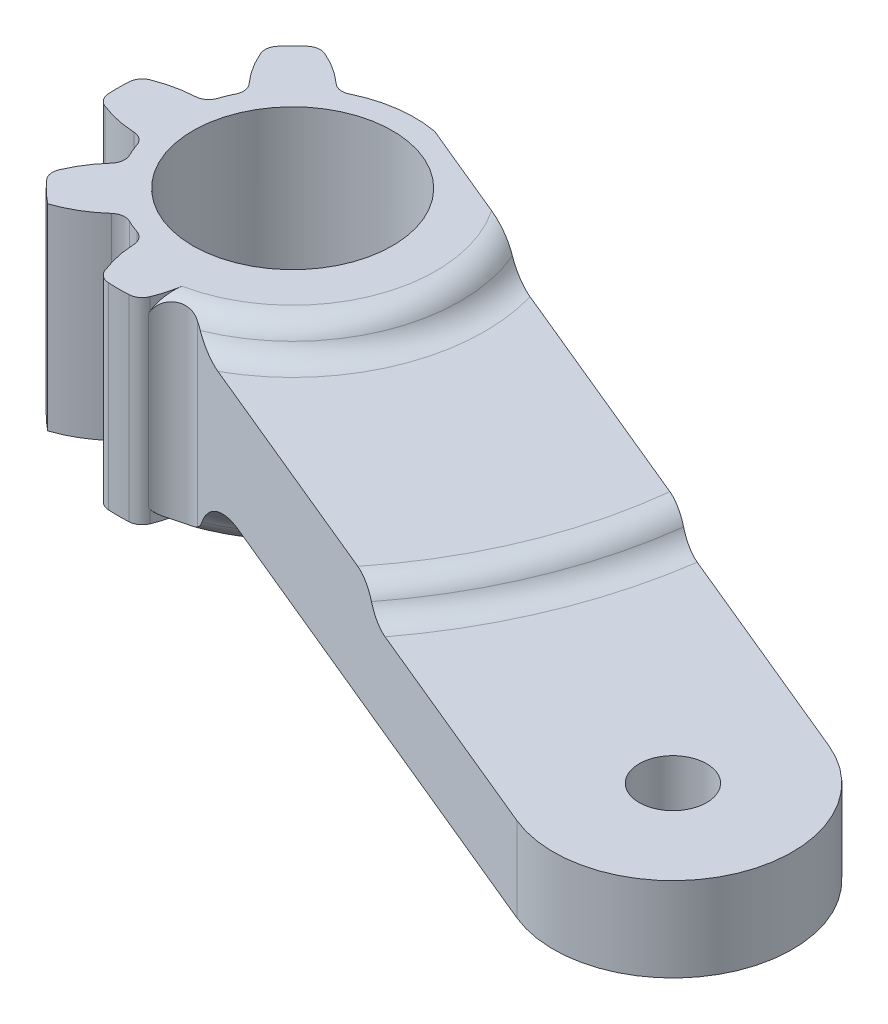
SolidWorks part; units mm, degrees
ref_plane "Front Plane" through (0, 0, 0) normal (0, 0, 1) x (1, 0, 0)
ref_plane "Top Plane" through (0, 0, 0) normal (0, 1, 0) x (1, 0, 0)
ref_plane "Right Plane" through (0, 0, 0) normal (1, 0, 0) x (0, 0, -1)
sketch "Sketch1" plane through (0, 0, 0) normal (0, 1, 0) x (1, 0, 0)
  line L0 (0, -4.35) -> (0, 4.35) construction
  line L3 (-3, 4.35) -> (3, 4.35) construction
  circle A2 centre (0, 0) radius 5.35 construction
  circle A3 centre (0, 10.7) radius 5.35 construction
  circle A4 centre (0, 10.7) radius 6.1 construction
  circle A5 centre (0, 10.7) radius 4.35 construction
  arc A7 (-3.9161, 1.8939) -> (-4.1083, 1.4299) centre (0, 0) ccw
  arc A8 (-0.8055, 5.8758) -> (-1.0948, 4.5554) centre (3, 4.35) ccw
  arc A9 (1.0948, 4.5554) -> (0.8055, 5.8758) centre (-3, 4.35) ccw
  arc A10 (0.3714, 6.1889) -> (-0.3714, 6.1889) centre (0, 0) ccw
  arc A11 (3.9954, 2.447) -> (4.7244, 3.5853) centre (0.9546, 5.1972) ccw
  arc A12 (4.6388, 4.1136) -> (4.1136, 4.6388) centre (0, 0) ccw
  arc A13 (3.5853, 4.7244) -> (2.447, 3.9954) centre (5.1972, 0.9546) ccw
  arc A14 (4.5554, -1.0948) -> (5.8758, -0.8055) centre (4.35, 3) ccw
  arc A15 (6.1889, -0.3714) -> (6.1889, 0.3714) centre (0, 0) ccw
  arc A16 (5.8758, 0.8055) -> (4.5554, 1.0948) centre (4.35, -3) ccw
  arc A17 (2.447, -3.9954) -> (3.5853, -4.7244) centre (5.1972, -0.9546) ccw
  arc A18 (4.1136, -4.6388) -> (4.6388, -4.1136) centre (0, 0) ccw
  arc A19 (4.7244, -3.5853) -> (3.9954, -2.447) centre (0.9546, -5.1972) ccw
  arc A20 (-1.0948, -4.5554) -> (-0.8055, -5.8758) centre (3, -4.35) ccw
  arc A21 (-0.3714, -6.1889) -> (0.3714, -6.1889) centre (0, 0) ccw
  arc A22 (0.8055, -5.8758) -> (1.0948, -4.5554) centre (-3, -4.35) ccw
  arc A23 (-3.9954, -2.447) -> (-4.7244, -3.5853) centre (-0.9546, -5.1972) ccw
  arc A24 (-4.6388, -4.1136) -> (-3.8788, -4.8368) centre (0, 0) ccw
  arc A25 (-3.8788, -4.8368) -> (-2.447, -3.9954) centre (-5.1972, -0.9546) ccw
  arc A26 (-4.5554, 1.0948) -> (-5.8758, 0.8055) centre (-4.35, -3) ccw
  arc A27 (-6.1889, 0.3714) -> (-6.1889, -0.3714) centre (0, 0) ccw
  arc A28 (-5.8758, -0.8055) -> (-4.5554, -1.0948) centre (-4.35, 3) ccw
  arc A29 (-2.447, 3.9954) -> (-3.5853, 4.7244) centre (-5.1972, 0.9546) ccw
  arc A30 (-4.1136, 4.6388) -> (-4.6388, 4.1136) centre (0, 0) ccw
  arc A31 (-4.7244, 3.5853) -> (-3.9954, 2.447) centre (-0.9546, 5.1972) ccw
  arc A32 (-4.1083, -1.4299) -> (-3.9161, -1.8939) centre (0, 0) ccw
  arc A33 (-1.8939, -3.9161) -> (-1.4299, -4.1083) centre (0, 0) ccw
  arc A34 (1.4299, -4.1083) -> (1.8939, -3.9161) centre (0, 0) ccw
  arc A35 (3.9161, -1.8939) -> (4.1083, -1.4299) centre (0, 0) ccw
  arc A36 (4.1083, 1.4299) -> (3.9161, 1.8939) centre (0, 0) ccw
  arc A37 (1.8939, 3.9161) -> (1.4299, 4.1083) centre (0, 0) ccw
  arc A38 (-1.4299, 4.1083) -> (-1.8939, 3.9161) centre (0, 0) ccw
  arc A39 (3.9954, -2.447) -> (3.9161, -1.8939) centre (4.3662, -2.1116) cw
  arc A40 (2.447, -3.9954) -> (1.8939, -3.9161) centre (2.1116, -4.3662) ccw
  arc A41 (-0.8055, -5.8758) -> (-0.3714, -6.1889) centre (-0.3414, -5.6898) ccw
  arc A42 (0.3714, -6.1889) -> (0.8055, -5.8758) centre (0.3414, -5.6898) ccw
  arc A43 (3.5853, -4.7244) -> (4.1136, -4.6388) centre (3.7819, -4.2647) ccw
  arc A44 (4.6388, -4.1136) -> (4.7244, -3.5853) centre (4.2647, -3.7819) ccw
  arc A45 (5.8758, -0.8055) -> (6.1889, -0.3714) centre (5.6898, -0.3414) ccw
  arc A46 (4.5554, -1.0948) -> (4.1083, -1.4299) centre (4.5805, -1.5942) ccw
  arc A47 (3.9954, 2.447) -> (3.9161, 1.8939) centre (4.3662, 2.1116) ccw
  arc A48 (4.5554, 1.0948) -> (4.1083, 1.4299) centre (4.5805, 1.5942) cw
  arc A49 (6.1889, 0.3714) -> (5.8758, 0.8055) centre (5.6898, 0.3414) ccw
  arc A50 (2.447, 3.9954) -> (1.8939, 3.9161) centre (2.1116, 4.3662) cw
  arc A51 (4.7244, 3.5853) -> (4.6388, 4.1136) centre (4.2647, 3.7819) ccw
  arc A52 (4.1136, 4.6388) -> (3.5853, 4.7244) centre (3.7819, 4.2647) ccw
  arc A53 (0.8055, 5.8758) -> (0.3714, 6.1889) centre (0.3414, 5.6898) ccw
  arc A54 (-0.8055, 5.8758) -> (-0.3714, 6.1889) centre (-0.3414, 5.6898) cw
  arc A55 (-1.0948, 4.5554) -> (-1.4299, 4.1083) centre (-1.5942, 4.5805) cw
  arc A56 (-1.0948, -4.5554) -> (-1.4299, -4.1083) centre (-1.5942, -4.5805) ccw
  arc A57 (-2.447, -3.9954) -> (-1.8939, -3.9161) centre (-2.1116, -4.3662) cw
  arc A58 (-4.7244, -3.5853) -> (-4.6388, -4.1136) centre (-4.2647, -3.7819) ccw
  arc A59 (-6.1889, -0.3714) -> (-5.8758, -0.8055) centre (-5.6898, -0.3414) ccw
  arc A60 (-3.9954, -2.447) -> (-3.9161, -1.8939) centre (-4.3662, -2.1116) ccw
  arc A61 (-4.5554, -1.0948) -> (-4.1083, -1.4299) centre (-4.5805, -1.5942) cw
  arc A62 (-5.8758, 0.8055) -> (-6.1889, 0.3714) centre (-5.6898, 0.3414) ccw
  arc A63 (-4.5554, 1.0948) -> (-4.1083, 1.4299) centre (-4.5805, 1.5942) ccw
  arc A64 (-3.9954, 2.447) -> (-3.9161, 1.8939) centre (-4.3662, 2.1116) cw
  arc A65 (-4.6388, 4.1136) -> (-4.7244, 3.5853) centre (-4.2647, 3.7819) ccw
  arc A66 (-3.5853, 4.7244) -> (-4.1136, 4.6388) centre (-3.7819, 4.2647) ccw
  arc A67 (-2.447, 3.9954) -> (-1.8939, 3.9161) centre (-2.1116, 4.3662) ccw
  arc A68 (1.0948, 4.5554) -> (1.4299, 4.1083) centre (1.5942, 4.5805) ccw
  arc A69 (1.0948, -4.5554) -> (1.4299, -4.1083) centre (1.5942, -4.5805) cw
  point P14 (0, 4.35)
  point P92 (-1.0976, 4.2093)
  point P119 (1.0976, 4.2093)
  dimension "D4" = 10.7
  dimension "D5" = 12.2
  dimension "D2" = 8.7
  dimension "D3" = 8.7
  dimension "D6" = 6.2
  dimension "D8" = 4.1
  dimension "D9" = 4.1
  dimension "D11" = 0.5
  dimension "D12" = 0.5
  dimension "D1" = 10.7
  dimension "D7" = 6
  dimension "D10" = 8
extrude "Boss-Extrude1" add sketch "Sketch1" along normal blind 7
sketch "Sketch2" plane through (0, 7, 0) normal (0, 1, 0) x (1, 0, 0)
  line L0 (0, 0) -> (23.097, -9.5671) construction
  line L1 (1.6264, 3.9265) -> (24.7234, -5.6406)
  line L2 (-1.6264, -3.9265) -> (21.4706, -13.4936)
  line L3 (0, 0) -> (0, 4.25) construction
  arc A0 (1.6264, 3.9265) -> (-1.6264, -3.9265) centre (0, 0) ccw
  arc A1 (21.4706, -13.4936) -> (24.7234, -5.6406) centre (23.097, -9.5671) ccw
  point P3 (11.5485, -4.7835)
  dimension "D1" = 112.5
  dimension "D2" = 25
  dimension "D3" = 8.5
extrude "Boss-Extrude2" add sketch "Sketch2" against normal blind 7
sketch "Sketch3" plane through (0, 7, 0) normal (0, 1, 0) x (1, 0, 0)
  line L13 (5.2516, 2.4249) -> (0.7696, 4.2814)
  line L14 (24.7234, -5.6406) -> (4.2957, 2.8208) construction
  line L15 (-3.9872, 6.2517) -> (-3.2325, 8.0738)
  line L16 (-3.2325, 8.0738) -> (6.0063, 4.247)
  line L17 (6.0063, 4.247) -> (5.2516, 2.4249)
  line L18 (-1.4299, 4.1083) -> (-3.9872, 6.2517)
  circle A0 centre (23.097, -9.5671) radius 1.2
  circle A1 centre (0, 0) radius 3.55
  arc A2 (-1.4299, 4.1083) -> (0.7696, 4.2814) centre (0, 0) cw
  dimension "D1" = 2.4
  dimension "D2" = 10
  dimension "D3" = 7.1
extrude "Cut-Extrude3" cut sketch "Sketch3" against normal blind 7
sketch "Sketch4" plane through (0, 0, 0) normal (0, -1, 0) x (1, 0, 0)
  line L0 (-3.2798, -1.3585) -> (14.9207, 6.1803) construction
  line L1 (24.7234, 5.6406) -> (0.7696, -4.2814) construction
  line L2 (0.7359, 3.4729) -> (12.2409, 7.3927)
  line L3 (13.8831, 3.4282) -> (2.9761, -1.9353)
  arc A0 (0.7359, 3.4729) -> (2.9761, -1.9353) centre (0, 0) ccw
  arc A1 (13.8831, 3.4282) -> (12.2409, 7.3927) centre (12.9343, 5.3576) ccw
  circle A2 centre (0, 0) radius 3.05 construction
  dimension "D1" = 7.1
  dimension "D2" = 4.3
  dimension "D4" = 6.1
  dimension "D3" = 19.7
extrude "Cut-Extrude4" cut sketch "Sketch4" against normal blind 4.5
sketch "Sketch7" plane through (0, 7, 0) normal (0, 1, 0) x (1, 0, 0)
  line L0 (24.7234, -5.6406) -> (0.7696, 4.2814) construction
  line L1 (1.0429, -5.0321) -> (21.4706, -13.4936) construction
  line L2 (5.6691, 2.2519) -> (28.6499, -7.267)
  line L3 (28.6499, -7.267) -> (25.3971, -15.12)
  line L4 (25.3971, -15.12) -> (2.4163, -5.601)
  arc A0 (5.6691, 2.2519) -> (2.4163, -5.601) centre (0, 0) cw
  arc A2 (21.4706, -13.4936) -> (24.7234, -5.6406) centre (23.097, -9.5671) ccw construction
  dimension "D1" = 6.1
extrude "Cut-Extrude5" cut sketch "Sketch7" against normal blind 1
sketch "Sketch8" plane through (0, 0, 0) normal (0, -1, 0) x (1, 0, 0)
  line L0 (1.0429, 5.0321) -> (21.4706, 13.4936) construction
  line L1 (24.7234, 5.6406) -> (0.7696, -4.2814) construction
  line L2 (2.4163, 5.601) -> (25.3971, 15.12)
  line L3 (25.3971, 15.12) -> (28.6499, 7.267)
  line L4 (28.6499, 7.267) -> (5.6691, -2.2519)
  arc A0 (2.4163, 5.601) -> (5.6691, -2.2519) centre (0, 0) cw
  arc A1 (24.7234, 5.6406) -> (21.4706, 13.4936) centre (23.097, 9.5671) ccw construction
  dimension "D1" = 6.1
extrude "Cut-Extrude6" cut sketch "Sketch8" against normal blind 2
sketch "Sketch9" plane through (0, 6, 0) normal (0, 1, 0) x (1, 0, 0)
  line L0 (0, 0) -> (23.097, -9.5671) construction
  line L5 (21.4706, -13.4936) -> (12.7683, -9.889)
  line L6 (2.4163, -5.601) -> (21.4706, -13.4936) construction
  line L8 (16.0211, -2.036) -> (24.7234, -5.6406)
  arc A0 (16.0211, -2.036) -> (12.7683, -9.889) centre (0, 0) cw
  arc A1 (24.7234, -5.6406) -> (21.4706, -13.4936) centre (23.097, -9.5671) cw
  arc A2 (12.2409, -7.3927) -> (13.8831, -3.4282) centre (12.9343, -5.3576) ccw construction
extrude "Cut-Extrude7" cut sketch "Sketch9" against normal blind 1
fillet "Fillet1" radius 1 2 edges at (5.9498, 0, -1.3451) (3.256, 0, 5.1583)
fillet "Fillet2" radius 2 2 edges at (5.9498, 2, -1.3451) (3.256, 2, 5.1583)
fillet "Fillet3" radius 1 2 edges at (14.9207, 6, 6.1803) (5.6357, 7, 2.3344)
fillet "Fillet4" radius 1 2 edges at (14.9207, 5, 6.1803) (5.6357, 6, 2.3344)
fillet "Fillet5" radius 1 1 edges at (1.0429, 3.5, 5.0321)
